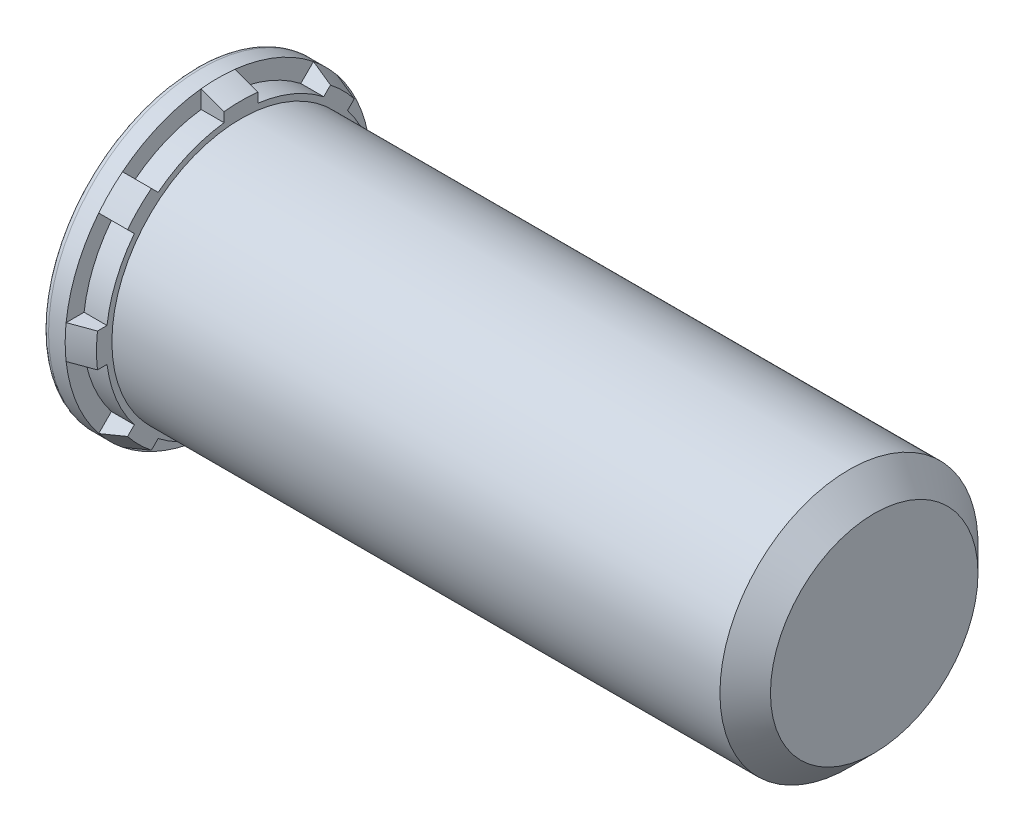
SolidWorks part; units mm, degrees
revolve "BaseBody" add sketch "BodySke" angle 360 about L6 other way angle 7.5
sketch "BodySke" plane through (0, 0, 0) normal (0, 0, 1) x (1, 0, 0)
  line L0 (-0.4286, 2.7407) -> (-0.4286, 0)
  line L1 (0.4286, 2.7015) -> (0.4286, 2.413)
  line L2 (0, 2.8575) -> (0.4286, 2.7015)
  line L3 (0.4286, 2.413) -> (11.7989, 2.413)
  line L4 (12.2714, 1.9406) -> (12.2714, 0)
  line L5 (12.2714, 0) -> (-0.4286, 0)
  line L6 (0, 0) -> (50.554, 0) construction
  line L7 (-0.4286, 2.7407) -> (-0.4261, 2.7407)
  line L8 (12.2714, 1.9406) -> (11.7989, 2.413)
  line L9 (-0.3118, 2.8575) -> (0, 2.8575)
  line L11 (0.7925, 19.05) -> (0.7925, -3.175) construction
  line L13 (-0.4261, 2.7407) -> (-0.4261, 2.7432)
  arc A0 (-0.4261, 2.7432) -> (-0.3118, 2.8575) centre (-0.3118, 2.7432) cw
  dimension "Fillet_rad" = 0.1143
  dimension "Minor_dia" = 3.8811
  dimension "Diameter" = 4.826
  dimension "H_dia" = 5.715
  dimension "Advance" = 0.7925
  dimension "D1" = 20
  dimension "Length" = 12.7
  dimension "D2" = 0.0025
  dimension "D3" = 0.0025
  dimension "Clinch_ht" = 0.4286
  dimension "Head_ht" = 0.8572
cosmetic thread "ThreadCosmetic" [suppressed] parameters "Thread_length"=10.16, "Thread_minor"=3.8811
ref_plane "Plane1" through (0, 0, 0) normal (0, 0, 1) x (1, 0, 0)
ref_plane "Plane2" through (0, 0, 0) normal (0, 1, 0) x (1, 0, 0)
ref_plane "Plane3" through (0, 0, 0) normal (1, 0, 0) x (0, 0, -1)
sketch "ThdSchSke" plane through (0, 0, 0) normal (0, 0, 1) x (1, 0, 0)
  line L0 (2.1114, -1.9406) -> (1.7806, -2.413)
  line L1 (2.1114, -1.9406) -> (2.4422, -2.413)
  line L2 (2.4422, -2.413) -> (2.4422, -3.0162)
  line L3 (-3.175, 0) -> (5.1513, 0) construction
  line L5 (2.4422, -3.0162) -> (1.7806, -3.0162)
  line L6 (1.7806, -3.0162) -> (1.7806, -2.413)
  line L7 (-0.4286, 2.7407) -> (-0.4286, -2.7407) construction
  dimension "Diameter" = 4.826
  dimension "Thread_minor" = 3.8811
  dimension "Start" = 2.54
revolve "ThreadSchematic" [suppressed] cut sketch "ThdSchSke" angle 360 about L3
pattern_linear "ThdSchPat" [suppressed]
sketch "RibCutSke" plane through (0.4286, 1.7944, -0.091) normal (1, 0, 0) x (0, 0, -1)
  line L0 (0.224, 0.71) -> (0.224, 1.0457)
  line L1 (1.4572, 0.1992) -> (1.6946, 0.4366)
  line L2 (0.224, 0.598) -> (0.224, 0.0891) construction
  line L3 (-0.091, -1.7944) -> (-0.091, 5.0239) construction
  line L4 (-0.091, -1.7944) -> (0.224, 0.598) construction
  line L5 (-0.091, -1.7944) -> (1.378, 0.12) construction
  line L6 (1.378, 0.12) -> (1.0232, -0.2348) construction
  arc A1 (1.4572, 0.1992) -> (0.224, 0.71) centre (-0.091, -1.7944) ccw
  arc A2 (1.6946, 0.4366) -> (0.224, 1.0457) centre (-0.091, -1.7944) ccw
  circle A3 centre (-0.091, -1.7944) radius 2.7015 construction
  circle A4 centre (-0.091, -1.7944) radius 2.413 construction
  dimension "Rib_root_half_angle" = 7.5
  dimension "Rib_root_gap_angle" = 30
  dimension "Angle" = 45
extrude "RibCut" cut sketch "RibCutSke" against normal blind 0.4286
pattern_circular "RibCutsPat" count 8 every 45 about axis through (0, 0, 0) along (1, 0, 0) of "RibCut"
equation "' \"Length@BodySke\" = 0.5"
equation "' \"H_dia@BodySke\" = 0.225"
equation "' \"Start@ThdSchSke\" = 0.1"
equation "' \"Diameter@BodySke\" = 0.19"
equation "' \"Minor_dia@BodySke\" = 0.1528"
equation "' \"Advance@BodySke\" = 0.0312"
equation "\"Fillet_rad@BodySke\" =   \"H_dia@BodySke\" *0.02"
equation "\"Clinch_ht@BodySke\" = \"H_dia@BodySke\" * 0.075"
equation "\"Head_ht@BodySke\" =  \"H_dia@BodySke\" * 0.15"
equation "\"Num_ribs@RibCutsPat\" = 8"
equation "\"Angle@RibCutSke\" =\"Angle@RibCutsPat\""
equation "\"Rib_root_half_angle@RibCutSke\" = \"Angle@RibCutSke\" / 6"
equation "\"Rib_root_gap_angle@RibCutSke\" = \"Angle@RibCutSke\" - (2 * \"Rib_root_half_angle@RibCutSke\" )"
equation "\"Rib_root_dia@RibCutSke\" = \"Diameter@BodySke\""
equation "\"Inner_dia@RibCutSke\" = \"Diameter@BodySke\" + ( \"H_dia@BodySke\" - \"Diameter@BodySke\" ) / 4"
equation "\"Outer_dia@RibCutSke\" = \"H_dia@BodySke\""
equation "\"Depth@RibCut\" = \"Clinch_ht@BodySke\""
equation "\"Thread_length@ThreadCosmetic\" = \"Length@BodySke\" - \"Start@ThdSchSke\""
equation "\"Thread_minor@ThreadCosmetic\" = \"Minor_dia@BodySke\""
equation "\"Thread_minor@ThdSchSke\" = \"Minor_dia@BodySke\""
equation "\"Diameter@ThdSchSke\" = \"Diameter@BodySke\""
equation "\"Overcut@ThdSchSke\" = \"Diameter@BodySke\" * 1.25"
equation "\"Num_threads@ThdSchPat\" = int( \"Thread_length@ThreadCosmetic\" / \"Advance@BodySke\" + 0.999 )  + 1"
equation "\"Advance@ThdSchPat\" = \"Thread_length@ThreadCosmetic\" /  (\"Num_threads@ThdSchPat\" - 1) 'relax it"
equation "\"Num_threads@ThdSchPat\" = \"Num_threads@ThdSchPat\" - sgn( \"Num_threads@ThdSchPat\" - 1) '---chamfered tips only---"
